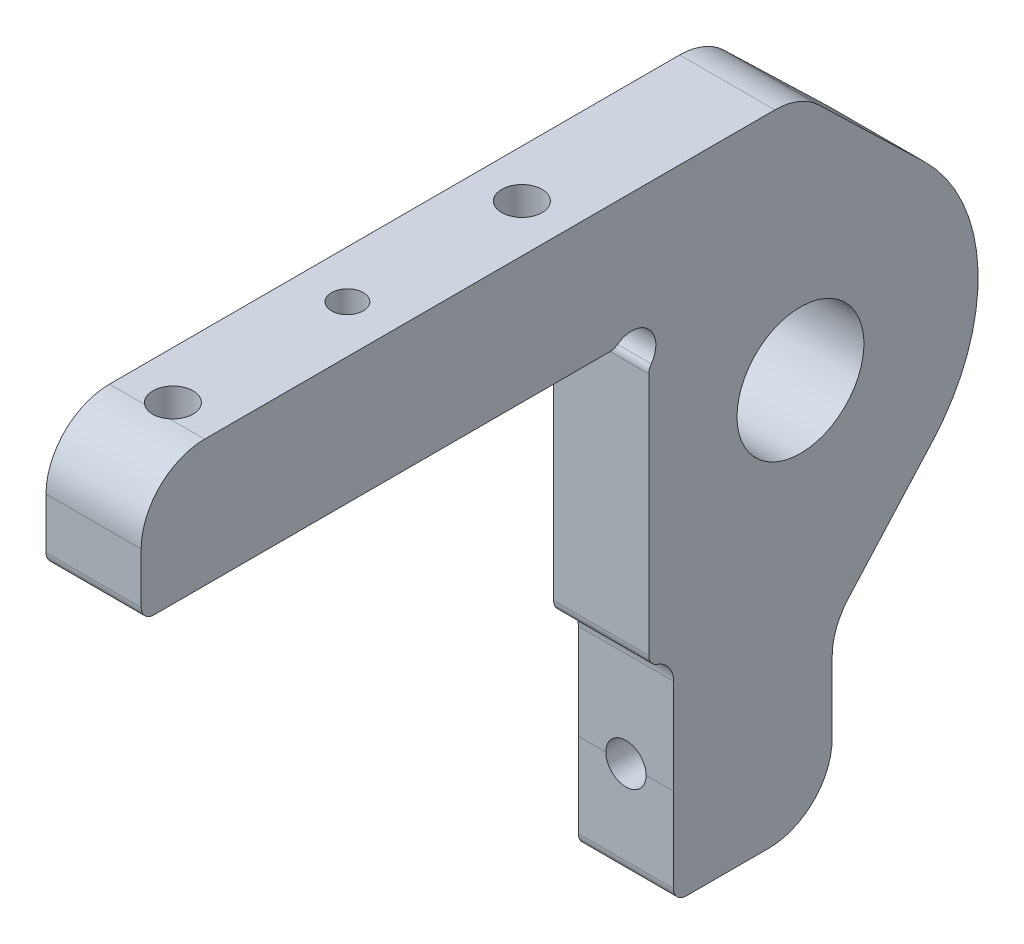
SolidWorks part; units mm, degrees
material "6061-T6 (SS)"
ref_plane "Front Plane" through (0, 0, 0) normal (0, 0, 1) x (1, 0, 0)
ref_plane "Top Plane" through (0, 0, 0) normal (0, 1, 0) x (1, 0, 0)
ref_plane "Right Plane" through (0, 0, 0) normal (1, 0, 0) x (0, 0, -1)
sketch "Sketch1" plane through (0, 0, 0) normal (1, 0, 0) x (0, 0, -1)
  line L0 (-56.0209, 0) -> (113.8933, 0) construction
  line L1 (-131.183, 34.9318) -> (0, 34.9318) construction
  line L2 (0, 34.9318) -> (0, 111.1318) construction
  line L3 (0, 111.1318) -> (-94.9437, 111.1318) construction
  line L4 (-131.183, 37.2178) -> (-2.286, 37.2178) construction
  line L5 (-2.286, 37.2178) -> (-2.286, 108.8458) construction
  line L6 (-2.286, 108.8458) -> (-94.9437, 108.8458) construction
  line L7 (-131.183, 37.2178) -> (-131.183, 34.9318) construction
  line L8 (-85.0265, 37.4083) -> (-34.2265, 37.4083) construction
  line L9 (-85.0265, 37.4083) -> (-85.0265, 88.2083) construction
  line L10 (-85.0265, 88.2083) -> (-34.2265, 88.2083) construction
  line L11 (-34.2265, 37.4083) -> (-34.2265, 88.2083) construction
  line L12 (-34.036, 56.2678) -> (-31.75, 56.2678) construction
  line L13 (-34.036, 56.2678) -> (-34.036, 37.2178) construction
  line L14 (-94.9437, 111.1318) -> (-94.9437, 108.8458) construction
  line L15 (-31.75, 56.2678) -> (-31.75, 37.2178) construction
  line L16 (-15.3961, 37.2178) -> (-15.3961, 34.9318) construction
  line L17 (-34.2265, 37.4083) -> (-34.2265, 37.2178) construction
  line L18 (-34.2265, 37.4083) -> (-34.036, 37.4083) construction
  line L19 (0, 152.4) -> (-175.0489, 152.4) construction
  line L20 (-19.05, 152.4) -> (-19.05, 76.2) construction
  line L21 (-19.05, 76.2) -> (-19.05, 0) construction
  line L22 (-85.0265, 88.2083) -> (-85.0265, 100.9083)
  line L24 (-31.75, 56.4583) -> (-31.75, 37.2178)
  line L25 (-31.75, 37.2178) -> (-15.875, 37.2178)
  line L28 (-85.0265, 100.9083) -> (-19.05, 100.9083)
  line L29 (-19.05, 100.9083) -> (-6.7037, 88.9944)
  line L33 (-34.2265, 58.8713) -> (-34.2265, 88.2083)
  line L34 (-34.2265, 88.2083) -> (-85.0265, 88.2083)
  line L38 (-85.1535, 73.7643) -> (-85.0265, 73.7643) construction
  line L40 (-15.875, 37.2178) -> (-15.875, 53.0928)
  line L41 (-15.875, 53.0928) -> (-5.8044, 64.339)
  line L42 (-34.163, 58.8713) -> (-34.2265, 58.8713)
  circle A0 centre (-19.05, 76.2) radius 7.9375 construction
  arc A1 (-6.7037, 88.9944) -> (-5.8044, 64.339) centre (-19.05, 76.2) cw
  circle A2 centre (-19.05, 76.2) radius 6.35
  arc A3 (-31.75, 56.4583) -> (-34.163, 58.8713) centre (-34.163, 56.4583) ccw
  dimension "D8" = 15.875
  dimension "D11" = 12.7
  dimension "D16" = 2.413
  dimension "D18" = 11.43
  dimension "D21" = 1.27
  dimension "D1" = 34.9318
  dimension "D2" = 76.2
  dimension "D4" = 19.05
  dimension "D5" = 0.1905
  dimension "D6" = 152.4
  dimension "D7" = 50.8
  dimension "D9" = 25.4
  dimension "D10" = 19.05
  dimension "D12" = 0.127
  dimension "D14" = 12.7
  dimension "D17" = 0.1905
  dimension "D19" = 15.875
  dimension "D20" = 15.875
  dimension "D22" = 31.75
  dimension "D3" = 2.286
extrude "Boss-Extrude1" add sketch "Sketch1" along normal blind 9.525
sketch "Sketch2" plane through (9.525, 0, 0) normal (1, 0, 0) x (0, 0, -1)
  line L0 (-34.2265, 84.7958) -> (-37.639, 88.2083) construction
  line L1 (-85.0265, 88.2083) -> (-34.2265, 88.2083) construction
  line L2 (-34.2265, 88.2083) -> (-34.2265, 58.8713) construction
  circle A2 centre (-35.9327, 86.5021) radius 2.413
  point P2 (0, 0)
  point P6 (-37.6408, 88.2083)
  point P9 (-34.2265, 84.8131)
  point P12 (-35.8472, 86.4206)
  dimension "D1" = 4.826
  dimension "D2" = 45
extrude "Cut-Extrude1" cut sketch "Sketch2" against normal through all
hole_wizard "#10-32 Tapped Hole2" positions "Sketch9" profile "Sketch10" tap size "#10-32" standard "ANSI Inch" end condition through all
sketch "Sketch9" plane through (0, 88.2083, 0) normal (0, -1, 0) x (-1, 0, 0)
  line L0 (-4.7625, -77.089) -> (-4.7625, -42.164) construction
  line L3 (-9.525, -85.0265) -> (-9.525, -37.639) construction
  line L6 (0, -85.0265) -> (0, -37.639) construction
  line L8 (0, -37.4015) -> (-9.525, -37.4015) construction
  line L10 (-9.525, -34.2265) -> (0, -34.2265) construction
  line L11 (-9.525, -85.0265) -> (0, -85.0265) construction
  line L12 (0, -85.0265) -> (0, -34.2265) construction
  line L13 (0, -85.0265) -> (0, -34.2265)
  line L14 (0, -59.6265) -> (-4.7625, -59.6265) construction
  circle A0 centre (-4.7625, -42.164) radius 3.9688 construction
  point P0 (-4.7625, -42.164)
  point P2 (-4.7625, -77.089)
  point P30 (-4.7625, -85.0265)
  point P38 (-4.7625, -59.6265)
  dimension "D2" = 7.9375
  dimension "D1" = 34.925
  dimension "D3" = 3.175
sketch "Sketch10" plane through (4.7625, 88.2083, 42.164) normal (1, 0, 0) x (0, 0, -1)
  line L0 (0, 0) -> (0, 12.7)
  line L1 (0, 12.7) -> (2.0193, 12.7)
  line L2 (2.0193, 12.7) -> (2.0193, 0)
  line L5 (2.0193, 0) -> (0, 0)
  line L11 (0, -6.35) -> (0, 107.95) construction
  dimension "Thru Tap Drill Dia." = 4.0386
  dimension "Thru Tap Drill Depth" = 12.7
cosmetic thread "Hole Thread2" parameters "D2"=4.826
cosmetic thread "Hole Thread3" parameters "D2"=4.826
hole_wizard "#10-32 Tapped Hole3" positions "Sketch11" profile "Sketch12" tap size "#10-32" standard "ANSI Inch" end condition through all
sketch "Sketch11" plane through (0, 0, 31.75) normal (0, 0, 1) x (1, 0, 0)
  line L5 (0, 37.4083) -> (9.525, 37.4083) construction
  line L6 (0, 37.4083) -> (0, 88.2083) construction
  line L7 (0, 37.4083) -> (0, 37.2178) construction
  line L8 (9.525, 56.4583) -> (9.525, 37.2178) construction
  line L10 (0, 40.5833) -> (9.525, 40.5833) construction
  line L11 (0, 37.4083) -> (0, 88.2083) construction
  line L13 (4.7625, 37.4083) -> (4.7625, 46.9333) construction
  circle A3 centre (4.7625, 46.9333) radius 3.9688
  point P27 (4.7625, 46.9333)
  dimension "D2" = 7.9375
  dimension "D1" = 3.175
  dimension "D3" = 9.525
sketch "Sketch12" plane through (4.7625, 46.9333, 31.75) normal (1, 0, 0) x (0, -1, 0)
  line L0 (0, 0) -> (0, 30.48)
  line L1 (0, 30.48) -> (2.0193, 30.48)
  line L2 (2.0193, 30.48) -> (2.0193, 0)
  line L5 (2.0193, 0) -> (0, 0)
  line L11 (0, -6.35) -> (0, 107.95) construction
  dimension "Thru Tap Drill Dia." = 4.0386
  dimension "Thru Tap Drill Depth" = 30.48
cosmetic thread "Hole Thread4" parameters "D2"=4.826
fillet "Fillet2" radius 6.35 4 edges at (4.7625, 37.2178, 15.875) (4.7625, 53.0928, 15.875) (4.7625, 100.9083, 19.05) (4.7625, 100.9083, 85.0265)
fillet "Fillet3" radius 1.27 5 edges at (4.7625, 37.2178, 31.75) (4.7625, 58.8713, 34.2265) (4.7625, 88.2083, 85.0265) (4.7625, 84.7958, 34.2265) (4.7625, 88.2083, 37.639)
sketch "Sketch14" plane through (0, 0, 31.75) normal (0, 0, 1) x (1, 0, 0)
  line L0 (0, 46.9333) -> (9.525, 46.9333)
  line L1 (0, 56.4583) -> (0, 38.4878) construction
  line L2 (9.525, 56.4583) -> (9.525, 38.4878) construction
  circle A0 centre (4.7625, 46.9333) radius 2.0193 construction
  point P6 (4.7625, 46.9333)
split line "Split Line2"
sketch "Sketch15" plane through (0, 88.2083, 0) normal (0, -1, 0) x (1, 0, 0)
  line L0 (4.7625, 77.089) -> (4.7625, 42.164) construction
  circle A0 centre (4.7625, 59.6265) radius 1.5875
  dimension "D1" = 3.175
extrude "Dowel Pin hole" cut sketch "Sketch15" against normal through all
